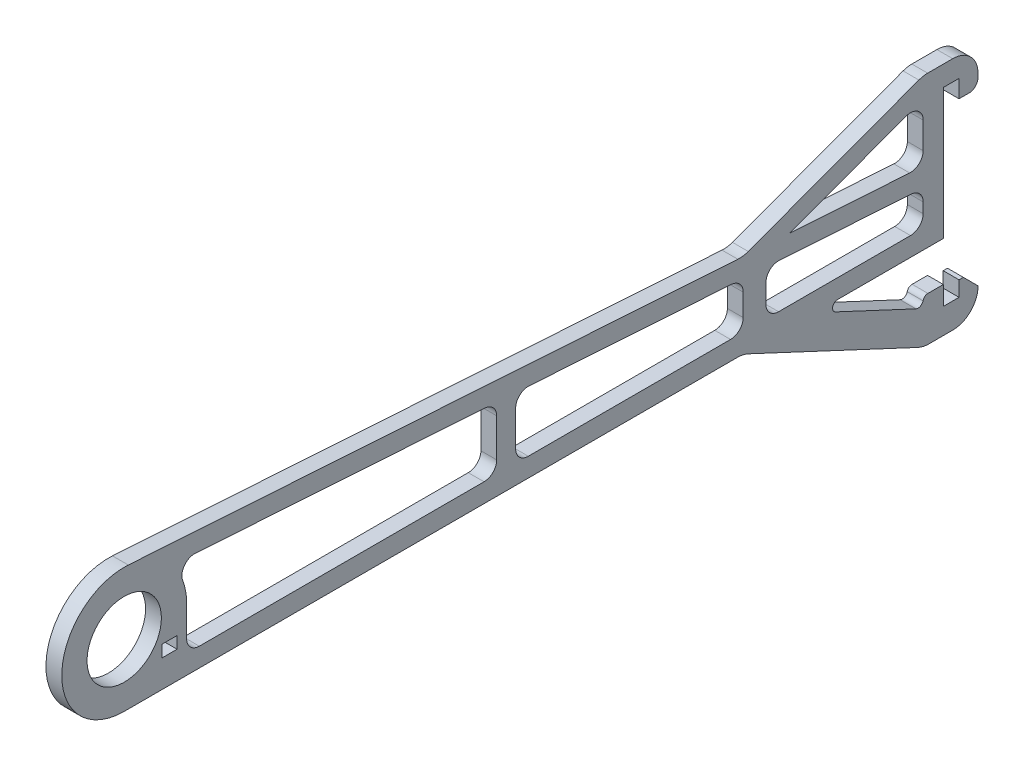
SolidWorks part; units mm, degrees
material "Delrin"
ref_plane "Front Plane" through (0, 0, 0) normal (0, 0, 1) x (1, 0, 0)
ref_plane "Top Plane" through (0, 0, 0) normal (0, 1, 0) x (1, 0, 0)
ref_plane "Right Plane" through (0, 0, 0) normal (1, 0, 0) x (0, 0, -1)
sketch "Sketch1" plane through (0, 0, 0) normal (1, 0, 0) x (0, 0, -1)
  line L0 (0.4103, 6.2604) -> (62.1851, 2.2118)
  line L1 (0, -6.2738) -> (62.1851, -6.2738)
  line L2 (80.264, 8.901) -> (83.2358, 8.901)
  line L3 (4.7788, 4.065) -> (80.264, -0.8821)
  line L4 (4.5027, -4.3688) -> (80.264, -4.3688)
  line L5 (-0.9662, 4.4415) -> (82.6296, -1.0372) construction
  line L6 (0, -4.3688) -> (80.264, -4.3688) construction
  line L7 (80.264, -6.2738) -> (80.264, 8.901) construction
  line L8 (5.3467, -3.556) -> (5.3467, -2.286) construction
  line L9 (5.3467, -2.286) -> (3.7592, -2.286) construction
  line L10 (3.7592, -3.556) -> (3.7592, -2.286) construction
  line L11 (5.3467, -3.556) -> (3.7592, -3.556) construction
  line L12 (5.3467, -3.556) -> (5.3467, -2.286) construction
  line L13 (5.3467, -2.286) -> (3.7592, -2.286) construction
  line L14 (3.7592, -3.556) -> (3.7592, -2.286) construction
  line L15 (5.3467, -3.556) -> (3.7592, -3.556) construction
  line L16 (6.2738, 0) -> (6.2738, -4.3688)
  line L17 (39.3251, 1.8009) -> (39.3251, -4.3688)
  line L18 (37.4201, 1.9258) -> (37.4201, -4.3688)
  line L19 (5.3086, -2.3241) -> (3.7973, -2.3241)
  line L20 (3.7973, -3.5179) -> (3.7973, -2.3241)
  line L21 (5.3086, -3.5179) -> (3.7973, -3.5179)
  line L22 (5.3086, -3.5179) -> (5.3086, -2.3241)
  line L23 (-0.8416, 6.3424) -> (82.7541, 0.8638) construction
  line L24 (84.8868, 5.091) -> (83.8708, 5.091)
  line L25 (83.8708, 5.091) -> (83.8708, 6.869)
  line L26 (83.8708, 6.869) -> (82.296, 6.869)
  line L27 (82.296, 6.869) -> (82.296, -6.2738)
  line L28 (82.296, -12.181) -> (83.8708, -12.181)
  line L29 (83.8708, -12.181) -> (83.8708, -10.657)
  line L30 (83.8708, -10.657) -> (84.3026, -10.657)
  line L31 (85.7758, -12.1302) -> (85.7758, -12.181)
  line L32 (83.2358, -14.721) -> (80.264, -14.721)
  line L33 (80.264, -14.721) -> (80.264, -6.2738) construction
  line L34 (85.7758, 5.98) -> (85.7758, 6.361)
  line L35 (84.3026, -10.657) -> (85.7758, -12.1302)
  line L36 (64.4711, 0.1529) -> (64.4711, -4.3688)
  line L37 (62.1851, 0.3027) -> (62.1851, -4.3688)
  line L38 (62.1851, 2.2118) -> (80.264, 8.901)
  line L39 (66.8488, 1.9062) -> (80.264, 6.8697)
  line L40 (62.1851, -6.2738) -> (80.264, -14.721)
  line L41 (69.3854, -6.2738) -> (80.264, -11.3567)
  line L42 (63.4754, -3.5124) -> (81.5543, -11.9596) construction
  line L43 (62.8461, 0.4252) -> (80.925, 7.1143) construction
  line L44 (69.3854, -6.2738) -> (80.264, -6.2738)
  line L45 (0, -6.2738) -> (80.264, -6.2738) construction
  line L46 (66.8488, 1.9062) -> (80.264, 1.027)
  line L47 (62.1851, -4.3688) -> (62.1851, 49995.6312) construction
  line L48 (80.264, 6.8697) -> (80.264, 1.027)
  line L49 (80.264, -0.8821) -> (80.264, -4.3688)
  line L50 (82.296, -12.181) -> (82.296, -10.276)
  line L51 (80.264, -6.2738) -> (82.296, -6.2738)
  line L52 (82.296, -10.276) -> (80.264, -10.276)
  line L53 (80.264, -10.276) -> (80.264, -11.3567)
  circle A0 centre (0, 0) radius 3.7338
  circle A1 centre (0, 0) radius 6.2738
  arc A2 (83.2358, 8.901) -> (85.7758, 6.361) centre (83.2358, 6.361) cw
  arc A3 (85.7758, -12.181) -> (83.2358, -14.721) centre (83.2358, -12.181) cw
  arc A4 (85.7758, 5.98) -> (84.8868, 5.091) centre (84.8868, 5.98) cw
  point P47 (85.7758, 8.901)
  point P50 (85.7758, -14.721)
  point P53 (85.7758, 5.091)
  point P54 (85.7758, -10.657)
  point P56 (85.7758, -10.657)
  dimension "D1" = 7.4676
  dimension "D2" = 2.54
  dimension "D3" = 5.842
  dimension "D8" = 1.5748
  dimension "D18" = 2.54
  dimension "D19" = 2.54
  dimension "D20" = 0.889
  dimension "D21" = 22.86
  dimension "D5" = 37.4201
  dimension "D10" = 1.905
  dimension "D11" = 1.778
  dimension "D12" = 1.905
  dimension "D4" = 5.3842
  dimension "D9" = 1.5748
  dimension "D14" = 1.524
  dimension "D15" = 3.81
  dimension "D16" = 4.064
  dimension "D17" = 1.905
  dimension "D22" = 19.05
  dimension "D23" = 80.264
  dimension "D24" = 2.032
  dimension "D25" = 2.286
  dimension "D29" = 1.905
  dimension "D6" = 1.905
  dimension "D7" = 1.905
  dimension "D13" = 0.0381
  dimension "D27" = 3.048
  dimension "D28" = 1.905
extrude "Boss-Extrude1" add sketch "Sketch1" along normal blind 1.5875 contours A1 L1 | A1 L4 L16 | L3 L18 L4 L17 | L31 L30 L29 L28 L27 L26 L25 L24 A4 L34 A2 L2 L7 L33 L32 A3 | A1 L21 L20 L19 L22 A0 | L3 L37 L4 L36 region at (0, 3.3483, -31.2395) region at (0, 5.4472, -2.7375) region at (0, -1.2526, -38.3694) region at (0, -3.3092, -5.7604) region at (0, -2.0703, -63.3219)
sketch "Sketch2" plane through (0, 0, -82.296) normal (0, 0, -1) x (-1, 0, 0)
  line L0 (-1.5875, 8.901) -> (0, 8.901) construction
  line L1 (-1.5875, 6.869) -> (0, 6.869) construction
  line L2 (-1.5875, -12.181) -> (0, -12.181) construction
  line L3 (-1.5875, -14.721) -> (0, -14.721) construction
  line L4 (-1.5875, 8.901) -> (0, 8.901)
  line L5 (-1.5875, 6.869) -> (0, 6.869)
  line L6 (-1.5875, -12.181) -> (0, -12.181)
  line L7 (-1.5875, -14.721) -> (0, -14.721)
  line L8 (-1.5875, 8.901) -> (-1.5875, 6.869)
  line L9 (0, 8.901) -> (0, 6.869)
  line L10 (-1.5875, -12.181) -> (-1.5875, -14.721)
  line L11 (0, -12.181) -> (0, -14.721)
fillet "Fillet1" radius 2.54 4 edges at (0.7937, 2.2118, -62.1851) (0.7937, 8.901, -80.264) (0.7937, -6.2738, -62.1851) (0.7937, -14.721, -80.264)
fillet "Fillet2" radius 1.27 14 edges at (0.7937, 4.065, -4.7788) (0.7937, -4.3688, -6.2738) (0.7937, -4.3688, -37.4201) (0.7937, 1.9258, -37.4201) (0.7937, 0.3027, -62.1851) (0.7937, -4.3688, -62.1851) (0.7937, -4.3688, -39.3251) (0.7937, 1.8009, -39.3251) (0.7937, 0.1529, -64.4711) (0.7937, -4.3688, -64.4711) (0.7937, 1.027, -80.264) (0.7937, 6.8697, -80.264) (0.7937, -0.8821, -80.264) (0.7937, -4.3688, -80.264)
fillet "Fillet3" radius 0.508 2 edges at (0.7937, -6.2738, -69.3854) (0.7937, -11.3567, -80.264)
fillet "Fillet4" radius 0.508 1 edges at (0.7937, -10.276, -80.264)
